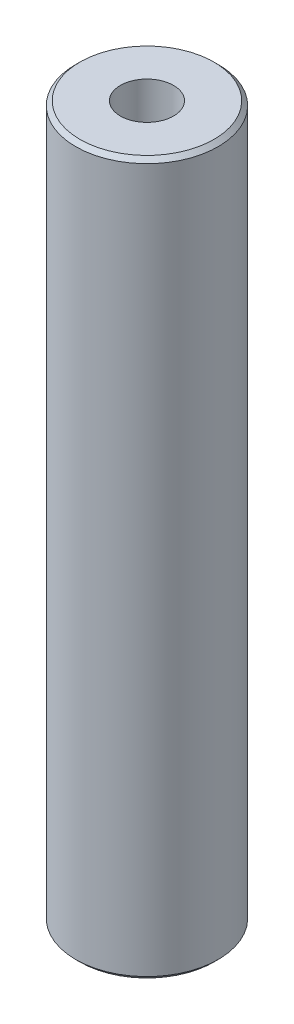
SolidWorks part; units mm, degrees
ref_plane "Front Plane" through (0, 0, 0) normal (0, 0, 1) x (1, 0, 0)
ref_plane "Top Plane" through (0, 0, 0) normal (0, 1, 0) x (1, 0, 0)
ref_plane "Right Plane" through (0, 0, 0) normal (1, 0, 0) x (0, 0, -1)
sketch "Sketch1" plane through (0, 0, 0) normal (0, 1, 0) x (1, 0, 0)
  circle A0 centre (0, 0) radius 60
  dimension "SHAFT_OD" = 120
extrude "Boss-Extrude1" add sketch "Sketch1" along normal blind 600
sketch "Sketch2" plane through (0, 0, 0) normal (0, 1, 0) x (1, 0, 0)
  circle A0 centre (0, 0) radius 22.382
  dimension "BORE_D" = 44.764
extrude "Cut-Extrude1" cut sketch "Sketch2" along normal through all
chamfer "Chamfer1" distance 3.517 angle 45.232 2 edges at (0, 600, 60) (0, 0, 60) first distance on face at (0, 600, 60) first distance on face at (0, 0, 22.382)
